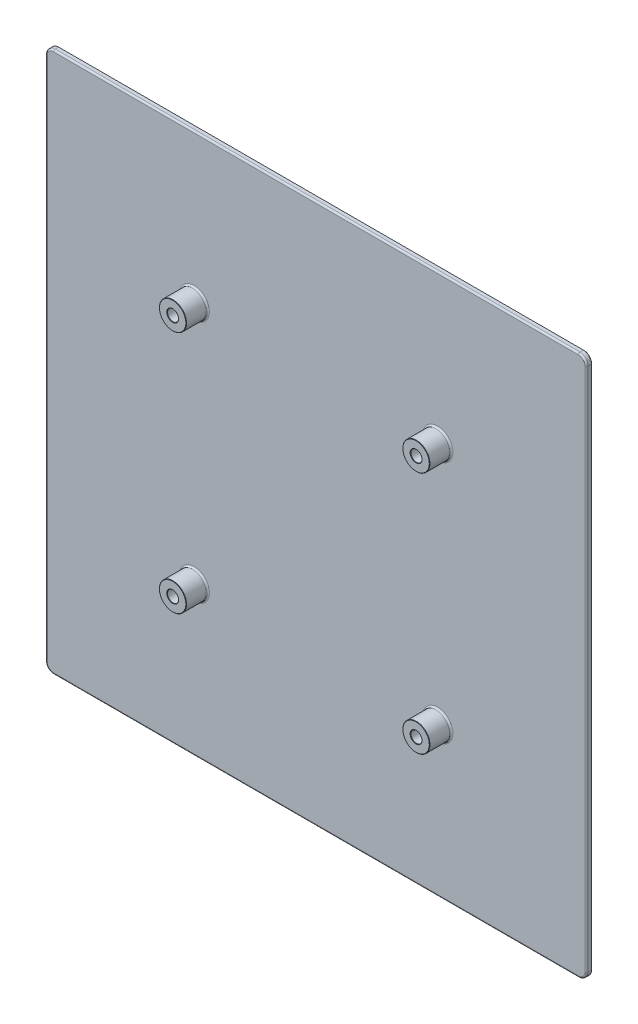
SolidWorks part; units mm, degrees
ref_plane "Alzado" through (0, 0, 0) normal (0, 0, 1) x (1, 0, 0)
ref_plane "Planta" through (0, 0, 0) normal (0, 1, 0) x (1, 0, 0)
ref_plane "Vista lateral" through (0, 0, 0) normal (1, 0, 0) x (0, 0, -1)
sketch "Croquis1" plane through (0, 0, 0) normal (0, 0, 1) x (1, 0, 0)
  line L1 (-100, -100) -> (100, -100)
  line L2 (-100, -100) -> (-100, 100)
  line L3 (-100, 100) -> (100, 100)
  line L4 (100, -100) -> (100, 100)
  line L5 (-100, -100) -> (100, 100) construction
  line L6 (-100, 100) -> (100, -100) construction
  line L7 (-45, -45) -> (45, -45) construction
  line L8 (-45, -45) -> (-45, 45) construction
  line L9 (-45, 45) -> (45, 45) construction
  line L10 (45, -45) -> (45, 45) construction
  line L11 (-45, -45) -> (45, 45) construction
  line L12 (-45, 45) -> (45, -45) construction
  circle A0 centre (-45, 45) radius 5
  circle A1 centre (-45, -45) radius 5
  circle A2 centre (45, -45) radius 5
  circle A3 centre (45, 45) radius 5
  point P0 (0, 0)
  point P6 (0, 0)
  dimension "D5" = 10
  dimension "D1" = 200
  dimension "D2" = 200
  dimension "D3" = 90
  dimension "D4" = 90
extrude "Saliente-Extruir1" add sketch "Croquis1" against normal blind 2 contours L1 L4 L3 L2 A3 L10 A2 L7 A1 L8 A0 L9 | L8 A1 L7 | L7 A2 L10 | L10 A3 L9 | L9 A0 L8 region at (0, 0, 0) region at (-45, 45, 0) region at (-45, -45, 0) region at (45, -45, 0) region at (45, 45, 0)
extrude "Saliente-Extruir2" add sketch "Croquis1<3>" along normal blind 8 contours L9 A0 L8 | L7 A2 L10 | L10 A3 L9 | A1 region at (-45, 45, 0) region at (45, -45, 0) region at (45, 45, 0)
sketch "Croquis1<3>" plane through (0, 0, 0) normal (0, 0, 1) x (1, 0, 0) same geometry as "Croquis1"
sketch "Croquis2" plane through (0, 0, 8) normal (0, 0, 1) x (1, 0, 0)
  circle A4 centre (-45, 45) radius 2.05
  circle A5 centre (45, 45) radius 2.05
  circle A7 centre (45, -45) radius 2.05
  circle A8 centre (-45, -45) radius 2.05
  point P8 (0, 0)
  dimension "D1" = 4.1
extrude "Cortar-Extruir1" cut sketch "Croquis2" against normal up to next
fillet "Redondeo1" radius 3 4 edges at (-100, 100, -1) (-100, -100, -1) (100, -100, -1) (100, 100, -1)
chamfer "Chaflán1" distance 0.14 angle 45 12 edges at (100, 0, -2) (0, 100, -2) (-100, 0, -2) (0, -100, -2) (-42.95, 45, -2) (47.05, 45, -2) (47.05, -45, -2) (-42.95, -45, -2) (-99.1213, -99.1213, -2) (99.1213, -99.1213, -2) (99.1213, 99.1213, -2) (-99.1213, 99.1213, -2)
fillet "Redondeo2" radius 0.6 12 edges at (99.1213, 99.1213, 0) (100, 0, 0) (99.1213, -99.1213, 0) (0, -100, 0) (-99.1213, -99.1213, 0) (-100, 0, 0) (-99.1213, 99.1213, 0) (0, 100, 0) (-40, 45, 0) (50, -45, 0) (50, 45, 0) (-40, -45, 0)
chamfer "Chaflán2" distance 0.14 angle 45 4 edges at (47.05, 45, 8) (-42.95, 45, 8) (-42.95, -45, 8) (47.05, -45, 8)
chamfer "Chaflán3" distance 0.12 angle 45 4 edges at (50, 45, 8) (-40, 45, 8) (-40, -45, 8) (50, -45, 8)
